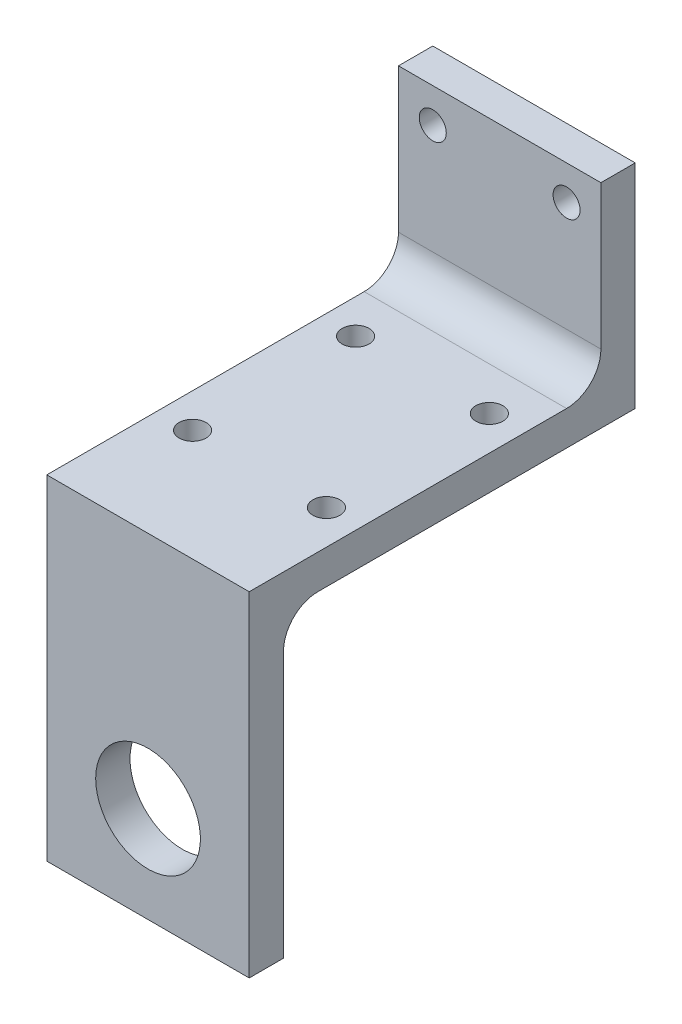
SolidWorks part; units mm, degrees
ref_plane "Front Plane" through (0, 0, 0) normal (0, 0, 1) x (1, 0, 0)
ref_plane "Top Plane" through (0, 0, 0) normal (0, 1, 0) x (1, 0, 0)
ref_plane "Right Plane" through (0, 0, 0) normal (1, 0, 0) x (0, 0, -1)
sketch "Sketch2" plane through (0, 0, 0) normal (1, 0, 0) x (0, 0, -1)
  line L3 (10.4198, -7.8348) -> (10.4198, 18.5812)
  line L4 (10.4198, 18.5812) -> (15.4998, 18.5812)
  line L5 (15.4998, 18.5812) -> (15.4998, -12.9148)
  line L6 (15.4998, -12.9148) -> (-41.6502, -12.9148)
  line L12 (10.4198, -7.8348) -> (-41.6502, -7.8348)
  line L13 (-41.6502, -7.8348) -> (-41.6502, -12.9148)
  line L15 (-41.6502, -12.9148) -> (-36.5702, -12.9148)
  line L16 (-41.6502, -12.9148) -> (-41.6502, -57.3648)
  line L17 (-41.6502, -57.3648) -> (-36.5702, -57.3648)
  line L18 (-36.5702, -12.9148) -> (-36.5702, -57.3648)
  dimension "D1" = 57.15
  dimension "D2" = 5.08
  dimension "D3" = 5.08
  dimension "D4" = 31.496
  dimension "D5" = 5.08
  dimension "D6" = 44.45
extrude "Boss-Extrude1" add sketch "Sketch2" along normal blind 29.972 contours L18 L6 L16 L17 | L3 L4 L5 L6 L13 L12 region at (0, -35.1398, 39.1102)
fillet "Fillet1" radius 5.08 2 edges at (14.986, -7.8348, -10.4198) (14.986, -12.9148, 36.5702)
sketch "Sketch3" plane through (0, 0, -15.4998) normal (0, 0, -1) x (-1, 0, 0)
  line L2 (-29.972, 18.5812) -> (0, 18.5812) construction
  circle A0 centre (-24.892, 13.5012) radius 2
  circle A1 centre (-5.08, 13.5012) radius 2
  circle A2 centre (-5.08, -10.6288) radius 4
  circle A3 centre (-24.892, -10.6288) radius 4
  dimension "D1" = 5.08
  dimension "D4" = 4
  dimension "D5" = 4
  dimension "D6" = 8
  dimension "D7" = 8
  dimension "D2" = 5.08
  dimension "D3" = 5.08
  dimension "D8" = 24.13
extrude "Cut-Extrude1" cut sketch "Sketch3" against normal up to surface (5.08 mm away) up to face at (14.986, 7.9132, -10.4198)
sketch "Sketch4" plane through (0, -12.9148, 0) normal (0, -1, 0) x (1, 0, 0)
  line L3 (29.972, -15.4998) -> (29.972, 31.4902) construction
  line L4 (0, -15.4998) -> (0, 31.4902) construction
  circle A0 centre (24.892, 1.0102) radius 2
  circle A1 centre (5.08, 1.0102) radius 2
  circle A2 centre (24.892, 25.1402) radius 2
  circle A3 centre (5.08, 25.1402) radius 2
  dimension "D1" = 4
  dimension "D2" = 4
  dimension "D3" = 4
  dimension "D4" = 4
  dimension "D5" = 5.08
  dimension "D6" = 5.08
  dimension "D7" = 24.13
  dimension "D8" = 16.51
extrude "Cut-Extrude2" cut sketch "Sketch4" against normal blind 29.972
sketch "Sketch5" plane through (0, 0, 36.5702) normal (0, 0, -1) x (-1, 0, 0)
  line L0 (-29.972, -57.3648) -> (0, -57.3648) construction
  circle A0 centre (-14.986, -43.1408) radius 7.75
  point P5 (-14.986, -57.3648)
  dimension "D1" = 15.5
  dimension "D2" = 30.226
extrude "Cut-Extrude3" cut sketch "Sketch5" against normal up to surface (5.08 mm away) up to face at (14.986, -32.5998, 41.6502)
